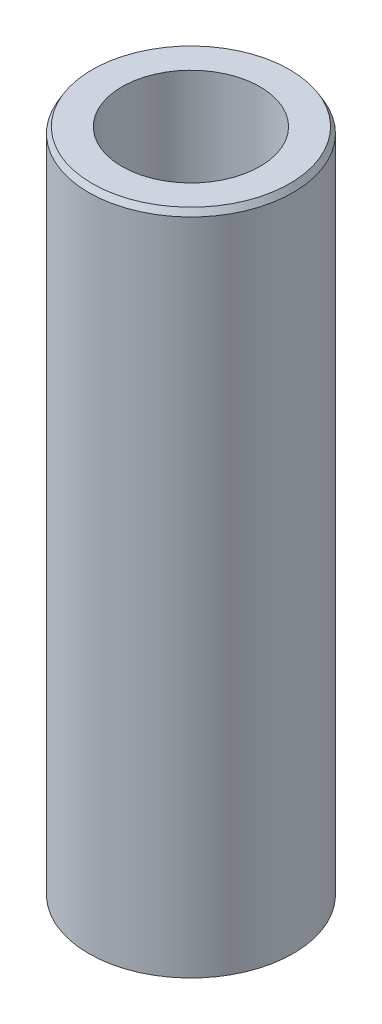
SolidWorks part; units mm, degrees
ref_plane "Front Plane" through (0, 0, 0) normal (0, 0, 1) x (1, 0, 0)
ref_plane "Top Plane" through (0, 0, 0) normal (0, 1, 0) x (1, 0, 0)
ref_plane "Right Plane" through (0, 0, 0) normal (1, 0, 0) x (0, 0, -1)
sketch "Sketch1" plane through (0, 0, 0) normal (0, 1, 0) x (1, 0, 0)
  circle A0 centre (0, 0) radius 60
  dimension "SHAFT_OD" = 120
extrude "Boss-Extrude1" add sketch "Sketch1" along normal blind 392.43
sketch "Sketch2" plane through (0, 0, 0) normal (0, 1, 0) x (1, 0, 0)
  circle A0 centre (0, 0) radius 40.5348
  dimension "BORE_D" = 81.0696
extrude "Cut-Extrude1" cut sketch "Sketch2" along normal through all
chamfer "Chamfer1" distance 3.5355 angle 30 2 edges at (0, 392.43, 60) (0, 0, 60) first distance on face at (0, 392.43, 60) first distance on face at (0, 0, 40.5348)
